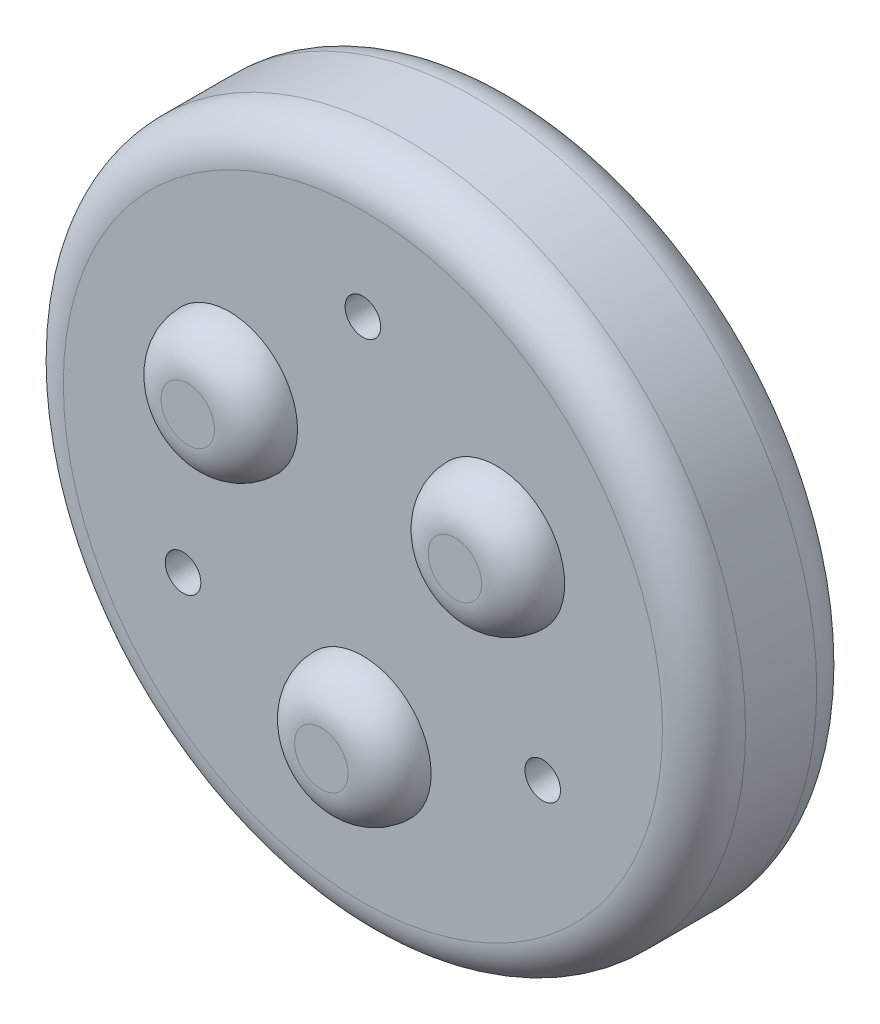
SolidWorks part; units mm, degrees
ref_plane "Спереди" through (0, 0, 0) normal (0, 0, 1) x (1, 0, 0)
ref_plane "Сверху" through (0, 0, 0) normal (0, 1, 0) x (1, 0, 0)
ref_plane "Справа" through (0, 0, 0) normal (1, 0, 0) x (0, 0, -1)
sketch "Эскиз1" plane through (0, 0, 0) normal (0, 0, 1) x (1, 0, 0)
  circle A0 centre (0, 0) radius 57.5
  dimension "D1" = 115
extrude "Бобышка-Вытянуть1" add sketch "Эскиз1" along normal blind 26 contours A0
fillet "Скругление2" radius 7 2 edges at (57.5, 0, 0) (57.5, 0, 26)
sketch "Эскиз2" plane through (0, 0, 0) normal (0, 0, 1) x (1, 0, 0)
  line L1 (0, 26) -> (-8, 26)
  line L2 (0, 26) -> (8, 26)
  line L3 (8, 26) -> (8, 43)
  line L4 (8, 43) -> (-8, 43)
  line L5 (-8, 26) -> (-8, 43)
  circle A0 centre (0, 0) radius 26
  point P4 (0, 43)
  dimension "D1" = 52
  dimension "D2" = 17
  dimension "D3" = 16
extrude "Вырез-Вытянуть1" cut sketch "Эскиз2" along normal blind 8.5 contours L4 L5 L1 L2 L3
sketch "Эскиз3" plane through (0, 0, 0) normal (0, 0, 1) x (1, 0, 0)
  line L0 (0, 0) -> (0, -26) construction
  line L1 (0, 0) -> (22.5167, 13) construction
  line L2 (0, 0) -> (-22.5167, 13) construction
  line L3 (0, 0) -> (0, 35) construction
  line L4 (22.5167, 13) -> (0, 13) construction
  line L5 (-22.5167, 13) -> (-22.5167, 24.5)
  line L6 (-22.5167, 24.5) -> (-22.5167, 1.5)
  line L7 (0, 0) -> (-30.3109, -17.5) construction
  circle A1 centre (0, 35) radius 3
  circle A2 centre (0, 35) radius 1.5
  circle A3 centre (0, 0) radius 35 construction
  circle A4 centre (0, 35) radius 3
  circle A5 centre (30.3109, -17.5) radius 3
  circle A6 centre (-30.3109, -17.5) radius 3
  circle A7 centre (0, 0) radius 26 construction
  circle A8 centre (-22.5167, 13) radius 11.5
  circle A9 centre (22.5167, 13) radius 11.5
  circle A10 centre (0, -26) radius 11.5
  point P2 (40.8365, -17.5)
  point P3 (0, 35)
  dimension "D1" = 52
  dimension "D2" = 23
  dimension "D3" = 70
  dimension "D5" = 6
  dimension "D6" = 3
  dimension "D4" = 120
  dimension "D7" = 120
extrude "Вырез-Вытянуть3" cut sketch "Эскиз3" along normal blind 91.5 contours A2
extrude "Вырез-Вытянуть4" cut sketch "Эскиз3<4>" along normal blind 14 contours A1
sketch "Эскиз3<4>" plane through (0, 0, 0) normal (0, 0, 1) x (1, 0, 0) same geometry as "Эскиз3"
extrude "Вырез-Вытянуть5" cut sketch "Эскиз3<6>" along normal blind 67 from offset 15 contours A1
sketch "Эскиз3<6>" plane through (0, 0, 0) normal (0, 0, 1) x (1, 0, 0) same geometry as "Эскиз3"
fillet "Скругление10" radius 3 1 edges at (8, 43, 4.25) type face fillet first side face at (8, 34.5, 4.25) second side face at (0, 43, 4.25)
fillet "Скругление11" radius 3 1 edges at (-8, 43, 4.25) type face fillet first side face at (-1.5, 43, 4.25) second side face at (-8, 34.5, 4.25)
fillet "Скругление12" radius 3 1 edges at (-8, 26, 4.25) type face fillet first side face at (-8, 33, 4.25) second side face at (0, 26, 4.25)
fillet "Скругление13" radius 3 1 edges at (8, 26, 4.25) type face fillet first side face at (1.5, 26, 4.25) second side face at (8, 33, 4.25)
extrude "Вырез-Вытянуть6" cut sketch "Эскиз3<8>" against normal blind 10 from offset 26 contours A6 | A5 | A1
sketch "Эскиз3<8>" plane through (0, 0, 0) normal (0, 0, 1) x (1, 0, 0) same geometry as "Эскиз3"
extrude "Бобышка-Вытянуть3" add sketch "Эскиз3<21>" along normal blind 7 from offset 26 contours A8
sketch "Эскиз3<21>" plane through (0, 0, 0) normal (0, 0, 1) x (1, 0, 0) same geometry as "Эскиз3"
fillet "Скругление30" radius 7 1 edges at (-11.0167, 13, 33) type face fillet first side face at (-11.0167, 13, 33) second side face at (-11.0167, 13, 33)
extrude "Бобышка-Вытянуть4" add sketch "Эскиз3<22>" along normal blind 7 from offset 26 contours A9
sketch "Эскиз3<22>" plane through (0, 0, 0) normal (0, 0, 1) x (1, 0, 0) same geometry as "Эскиз3"
extrude "Бобышка-Вытянуть5" add sketch "Эскиз3<23>" along normal blind 7 from offset 26 contours A10
sketch "Эскиз3<23>" plane through (0, 0, 0) normal (0, 0, 1) x (1, 0, 0) same geometry as "Эскиз3"
fillet "Скругление32" radius 7 1 edges at (34.0167, 13, 33) type face fillet first side face at (34.0167, 13, 33) second side face at (34.0167, 13, 33)
fillet "Скругление33" radius 7 1 edges at (11.5, -26, 33) type face fillet first side face at (11.5, -26, 33) second side face at (11.5, -26, 33)
